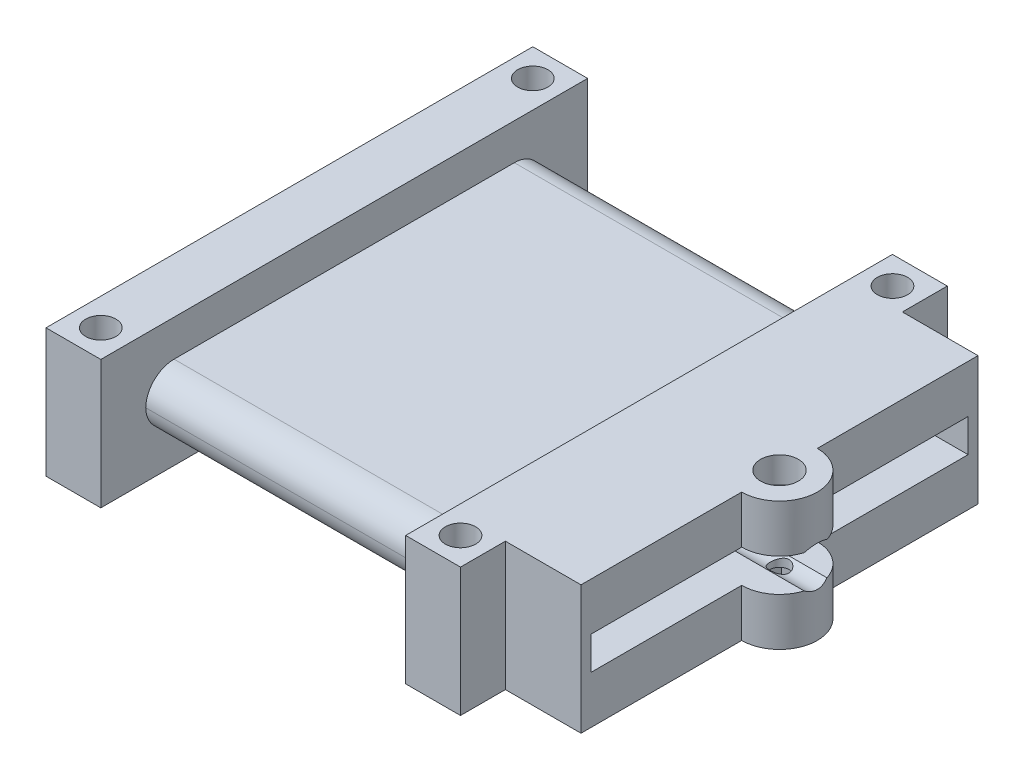
SolidWorks part; units mm, degrees
ref_plane "Front Plane" through (0, 0, 0) normal (0, 0, 1) x (1, 0, 0)
ref_plane "Top Plane" through (0, 0, 0) normal (0, 1, 0) x (1, 0, 0)
ref_plane "Right Plane" through (0, 0, 0) normal (1, 0, 0) x (0, 0, -1)
sketch "Sketch1" plane through (0, 0, 0) normal (1, 0, 0) x (0, 0, -1)
  line L0 (21, 5.9) -> (21, 0) construction
  line L1 (0, 0) -> (42, 0)
  line L2 (0, 0) -> (0, 5.9)
  line L3 (0, 5.9) -> (42, 5.9)
  line L4 (42, 0) -> (42, 5.9)
  line L6 (1.05, 1.2) -> (40.95, 1.2)
  line L7 (1.05, 1.2) -> (1.05, 4.7)
  line L8 (1.05, 4.7) -> (40.95, 4.7)
  line L9 (40.95, 1.2) -> (40.95, 4.7)
  line L10 (1.05, 1.2) -> (40.95, 4.7) construction
  line L11 (1.05, 4.7) -> (40.95, 1.2) construction
  point P7 (21, 2.95)
  dimension "D1" = 42
  dimension "D2" = 5.9
  dimension "D3" = 3.5
  dimension "D4" = 39.9
extrude "Boss-Extrude1" add sketch "Sketch1" along normal blind 32.25
fillet "Fillet2" radius 3 4 edges at (16.125, 0, -42) (16.125, 0, 0) (16.125, 5.9, 0) (16.125, 5.9, -42)
sketch "Sketch2" plane through (32.25, 0, 0) normal (1, 0, 0) x (0, 0, -1)
  line L0 (21, 5.9) -> (21, 0) construction
  line L1 (39, 5.9) -> (3, 5.9) construction
  line L2 (3, 0) -> (39, 0) construction
  line L4 (-4.75, -3.85) -> (46.75, -3.85)
  line L5 (-4.75, -3.85) -> (-4.75, 9.75)
  line L6 (-4.75, 9.75) -> (46.75, 9.75)
  line L7 (46.75, -3.85) -> (46.75, 9.75)
  line L8 (-4.75, -3.85) -> (46.75, 9.75) construction
  line L9 (-4.75, 9.75) -> (46.75, -3.85) construction
  line L14 (40.95, 1.2) -> (1.05, 1.2)
  line L15 (40.95, 1.2) -> (40.95, 4.7)
  line L16 (40.95, 4.7) -> (1.05, 4.7)
  line L17 (1.05, 1.2) -> (1.05, 4.7)
  line L18 (40.95, 1.2) -> (1.05, 4.7) construction
  line L19 (40.95, 4.7) -> (1.05, 1.2) construction
  point P6 (21, 2.95)
  point P11 (21, 2.95)
  point P12 (21, 2.95)
  dimension "D1" = 13.6
  dimension "D2" = 51.5
extrude "Boss-Extrude2" add sketch "Sketch2" along normal blind 5.8
sketch "Sketch3" plane through (0, 0, 0) normal (-1, 0, 0) x (0, 0, 1)
  line L0 (-21, 5.9) -> (-21, 0) construction
  line L1 (-39, 5.9) -> (-3, 5.9) construction
  line L2 (-3, 0) -> (-39, 0) construction
  line L4 (4.75, -3.85) -> (-46.75, -3.85)
  line L5 (4.75, -3.85) -> (4.75, 9.75)
  line L6 (4.75, 9.75) -> (-46.75, 9.75)
  line L7 (-46.75, -3.85) -> (-46.75, 9.75)
  line L8 (4.75, -3.85) -> (-46.75, 9.75) construction
  line L9 (4.75, 9.75) -> (-46.75, -3.85) construction
  line L10 (-1.05, 1.2) -> (-40.95, 1.2)
  line L11 (-1.05, 1.2) -> (-1.05, 4.7)
  line L12 (-1.05, 4.7) -> (-40.95, 4.7)
  line L13 (-40.95, 1.2) -> (-40.95, 4.7)
  line L14 (-1.05, 1.2) -> (-40.95, 4.7) construction
  line L15 (-1.05, 4.7) -> (-40.95, 1.2) construction
  point P6 (-21, 2.95)
  point P12 (-21, 2.95)
extrude "Boss-Extrude3" add sketch "Sketch3" along normal blind 5.8
sketch "Sketch4" plane through (0, 9.75, 0) normal (0, 1, 0) x (1, 0, 0)
  line L0 (-2.9, 46.75) -> (-2.9, 43.85) construction
  line L1 (-5.8, 46.75) -> (0, 46.75) construction
  line L2 (35.15, 46.75) -> (35.15, 43.85) construction
  line L3 (38.05, 46.75) -> (32.25, 46.75) construction
  line L4 (-2.9, -4.75) -> (-2.9, -1.85) construction
  line L5 (-5.8, -4.75) -> (0, -4.75) construction
  line L6 (35.15, -4.75) -> (35.15, -1.85) construction
  line L7 (38.05, -4.75) -> (32.25, -4.75) construction
  circle A0 centre (-2.9, 43.85) radius 1.6
  circle A1 centre (35.15, 43.85) radius 1.6
  circle A2 centre (-2.9, -1.85) radius 1.6
  circle A3 centre (35.15, -1.85) radius 1.6
  dimension "D2" = 3.2
  dimension "D4" = 3.2
  dimension "D6" = 3.2
  dimension "D8" = 3.2
  dimension "D1" = 2.9
  dimension "D3" = 2.9
  dimension "D5" = 2.9
  dimension "D7" = 2.9
extrude "Cut-Extrude1" cut sketch "Sketch4" against normal through all
sketch "Sketch6" plane through (38.05, 0, 0) normal (1, 0, 0) x (0, 0, -1)
  line L0 (46.75, -3.85) -> (46.75, 9.75) construction
  line L1 (-4.75, -3.85) -> (46.75, -3.85)
  line L2 (-4.75, -3.85) -> (-4.75, 3.35)
  line L3 (-4.75, 3.35) -> (46.75, 3.35)
  line L4 (46.75, -3.85) -> (46.75, 3.35)
  dimension "D1" = 7.2
extrude "Cut-Extrude2" [suppressed] cut sketch "Sketch6" against normal blind 5.8
sketch "Sketch7" plane through (-5.8, 0, 0) normal (-1, 0, 0) x (0, 0, 1)
  line L0 (4.75, -3.85) -> (4.75, 9.75) construction
  line L1 (-46.75, -3.85) -> (4.75, -3.85)
  line L2 (-46.75, -3.85) -> (-46.75, 3.35)
  line L3 (-46.75, 3.35) -> (4.75, 3.35)
  line L4 (4.75, -3.85) -> (4.75, 3.35)
  dimension "D1" = 7.2
extrude "Cut-Extrude3" [suppressed] cut sketch "Sketch7" against normal blind 5.8
sketch "Sketch8" plane through (0, 9.75, 0) normal (0, 1, 0) x (1, 0, 0)
  line L1 (0, 41.9996) -> (32.25, 41.9996) construction
  line L2 (38.05, 46.75) -> (38.05, -4.75) construction
  line L3 (46.05, 25) -> (46.05, 41.9996)
  line L4 (46.05, 41.9996) -> (38.05, 41.9996)
  line L5 (46.05, 17) -> (46.05, 0.0004)
  line L6 (46.05, 0.0004) -> (38.05, 0.0004)
  line L12 (-42.1211, 21) -> (79.5205, 21) construction
  line L13 (-5.8, -4.75) -> (-5.8, 46.75) construction
  circle A0 centre (46.05, 21) radius 4
  point P17 (-5.8, 21)
  line M5 (38.05, -4.75) -> (38.05, 46.75)
  dimension "D1" = 8
  dimension "D2" = 8
extrude "Boss-Extrude4" add sketch "Sketch8" against normal blind 13.6 contours A0 L3 L4 M5 | A0 L6 L5 M5 | A0 | A0 L12 region at (41.8639, 9.75, -32.2114) region at (46.05, 9.75, -22.6977) region at (46.05, 9.75, -19.3023) region at (41.8639, 9.75, -9.7886)
hole_wizard "CSK for M2 Flat Head Machine Screw1" positions "Sketch12" profile "Sketch13" countersink size "M2" standard "ANSI Metric" end condition through all
sketch "Sketch12" plane through (0, 9.75, 0) normal (0, 1, 0) x (1, 0, 0)
  point P0 (46.05, 21)
sketch "Sketch13" plane through (46.05, 9.75, -21) normal (1, 0, 0) x (0, 0, 1)
  line L0 (0, 0) -> (0, 13.6)
  line L1 (0, 13.6) -> (1, 13.6)
  line L2 (1, 13.6) -> (1, 3.75)
  line L3 (1, 3.75) -> (2, 2.75)
  line L4 (2, 2.75) -> (2, 0)
  line L6 (2, 0) -> (0, 0)
  line L7 (-1, 3.75) -> (-2, 2.75) construction
  line L11 (0, -6.35) -> (0, 107.95) construction
  dimension "Thru Hole Dia." = 2
  dimension "Thru Hole Depth" = 13.6
  dimension "C'Sink Dia." = 4
  dimension "C'Sink Angle" = 90
  dimension "Head Clearance" = 2.75
sketch "Sketch14" plane through (0, -3.85, 0) normal (0, -1, 0) x (1, 0, 0)
  line L1 (43.6716, -20.5274) -> (44.4516, -22.8234)
  line L2 (44.4516, -22.8234) -> (46.8299, -23.296)
  line L3 (46.8299, -23.296) -> (48.4284, -21.4726)
  line L4 (48.4284, -21.4726) -> (47.6484, -19.1766)
  line L5 (47.6484, -19.1766) -> (45.2701, -18.704)
  line L6 (45.2701, -18.704) -> (43.6716, -20.5274)
  circle A0 centre (46.05, -21) radius 2.1 construction
  dimension "D1" = 4.2
extrude "Cut-Extrude4" cut sketch "Sketch14" against normal blind 4
sketch "Sketch15" plane through (-5.8, 0, 0) normal (-1, 0, 0) x (0, 0, 1)
  line L1 (-40.95, 1.2) -> (-1.05, 1.2)
  line L2 (-40.95, 1.2) -> (-40.95, 4.7)
  line L3 (-40.95, 4.7) -> (-1.05, 4.7)
  line L4 (-1.05, 1.2) -> (-1.05, 4.7)
  line L5 (-46.75, -3.85) -> (-40.95, -3.85)
  line L6 (-46.75, -3.85) -> (-46.75, -1.85)
  line L7 (-46.75, -1.85) -> (-40.95, -1.85)
  line L8 (-40.95, -3.85) -> (-40.95, -1.85)
  line L9 (4.75, -3.85) -> (-1.05, -3.85)
  line L10 (4.75, -3.85) -> (4.75, -1.85)
  line L11 (4.75, -1.85) -> (-1.05, -1.85)
  line L12 (-1.05, -3.85) -> (-1.05, -1.85)
  dimension "D1" = 5.8
  dimension "D2" = 2
  dimension "D3" = 5.8
  dimension "D4" = 2
extrude "Cut-Extrude5" cut sketch "Sketch15" against normal through all contours L2 L1 L4 L3
sketch "Sketch17" plane through (-5.8, 0, 0) normal (-1, 0, 0) x (0, 0, 1)
  line L0 (-21, 4.7) -> (-21, 1.2) construction
  line L1 (-1.05, 4.7) -> (-40.95, 4.7) construction
  line L2 (-40.95, 1.2) -> (-1.05, 1.2) construction
  circle A0 centre (-21, 2.95) radius 2.125
  dimension "D1" = 4.25
extrude "Cut-Extrude6" cut sketch "Sketch17" against normal through all
